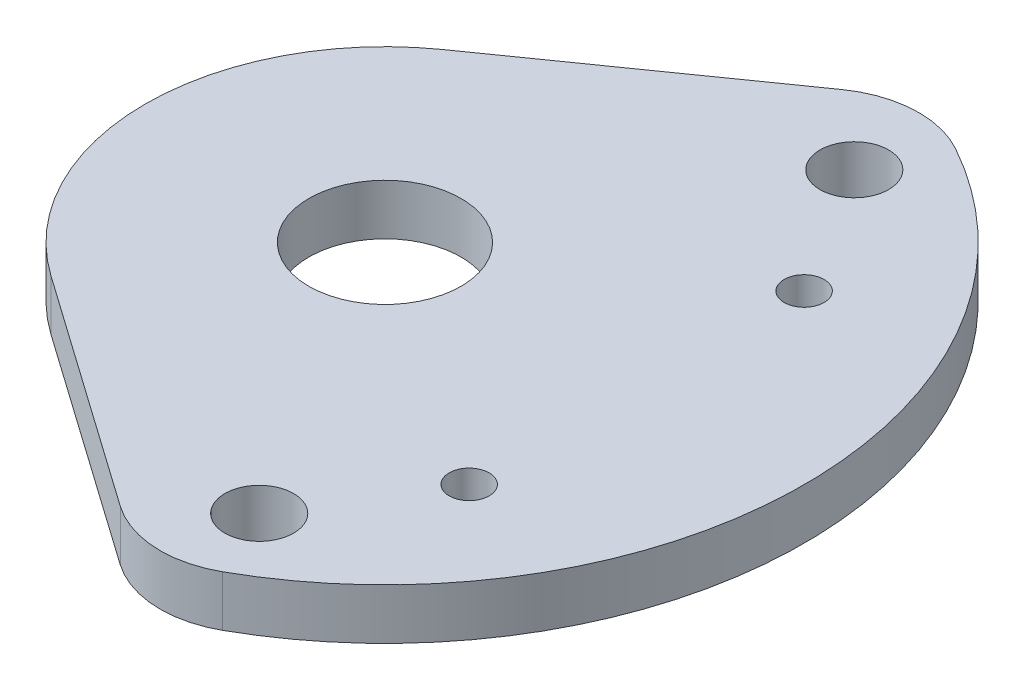
SolidWorks part; units mm, degrees
material "6061 Alloy"
ref_plane "Front Plane" through (0, 0, 0) normal (0, 0, 1) x (1, 0, 0)
ref_plane "Top Plane" through (0, 0, 0) normal (0, 1, 0) x (1, 0, 0)
ref_plane "Right Plane" through (0, 0, 0) normal (1, 0, 0) x (0, 0, -1)
sketch "Sketch1" plane through (0, 0, 0) normal (0, 1, 0) x (1, 0, 0)
  line L0 (0, 0) -> (8.978, -24.6669) construction
  line L6 (0, 0) -> (8.978, 24.6669) construction
  line L7 (0, 0) -> (-26.25, 0) construction
  line L8 (8.978, -24.6669) -> (-8.6358, -12.2647)
  line L9 (8.978, 24.6669) -> (-8.6358, 12.2647)
  circle A2 centre (0, 0) radius 4.7625
  circle A3 centre (0, 0) radius 26.25
  circle A4 centre (0, 0) radius 15
  dimension "D3" = 110
  dimension "D5" = 52.5
  dimension "D6" = 9.525
  dimension "D1" = 30
  dimension "D2" = 110
extrude "Boss-Extrude1" add sketch "Sketch1" along normal mid plane 3.175 contours A3 | A4 L8 A3 L9 | A4 A2 region at (0.519, 0, 17.9718) region at (-14.5757, 0, 0)
hole_wizard "M4 Clearance Hole1" positions "Sketch6" profile "Sketch7" hole size "M4" standard "ANSI Metric" end condition up to next
sketch "Sketch6" plane through (0, 1.5875, 0) normal (0, 1, 0) x (1, 0, 0)
  line L0 (0, 0) -> (10.75, 18.6195)
  line L1 (0, 0) -> (10.75, -18.6195)
  line L2 (0, 0) -> (-21.5, 0)
  point P2 (10.75, 18.6195)
  point P10 (10.75, -18.6195)
  dimension "D1" = 21.5
  dimension "D2" = 120
  dimension "D3" = 120
sketch "Sketch7" plane through (10.75, 1.5875, 18.6195) normal (1, 0, 0) x (0, 0, 1)
  line L0 (0, 0) -> (0, 3.175)
  line L1 (0, 3.175) -> (2.15, 3.175)
  line L2 (2.15, 3.175) -> (2.15, 0)
  line L5 (2.15, 0) -> (0, 0)
  line L11 (0, -6.35) -> (0, 107.95) construction
  dimension "Thru Hole Dia." = 4.3
  dimension "Thru Hole Depth" = 3.175
hole_wizard "M3x0.5 Tapped Hole1" positions "Sketch8" profile "Sketch9" tap size "M3x0.5" standard "ANSI Metric" end condition up to next
sketch "Sketch8" plane through (0, 1.5875, 0) normal (0, 1, 0) x (1, 0, 0)
  line L2 (-1000, 0) -> (49000, 0) construction
  line L3 (0, 0) -> (15.75, 0) construction
  line L5 (15.75, -10.48) -> (15.75, 10.48) construction
  point P20 (0, 0)
  point P47 (15.75, -10.48)
  point P50 (15.75, 10.48)
  dimension "D1" = 15.75
  dimension "D2" = 90
  dimension "D3" = 20.96
sketch "Sketch9" plane through (0, 1.5875, 0) normal (1, 0, 0) x (0, 0, 1)
  line L0 (0, 0) -> (0, 3.175)
  line L1 (0, 3.175) -> (1.25, 3.175)
  line L2 (1.25, 3.175) -> (1.25, 0)
  line L5 (1.25, 0) -> (0, 0)
  line L11 (0, -6.35) -> (0, 107.95) construction
  dimension "Thru Tap Drill Dia." = 2.5
  dimension "Thru Tap Drill Depth" = 3.175
cosmetic thread "Hole Thread1" parameters "D2"=3
cosmetic thread "Hole Thread6" parameters "D2"=3
fillet "Fillet1" radius 6.35 2 edges at (8.978, 0, -24.6669) (8.978, 0, 24.6669)
